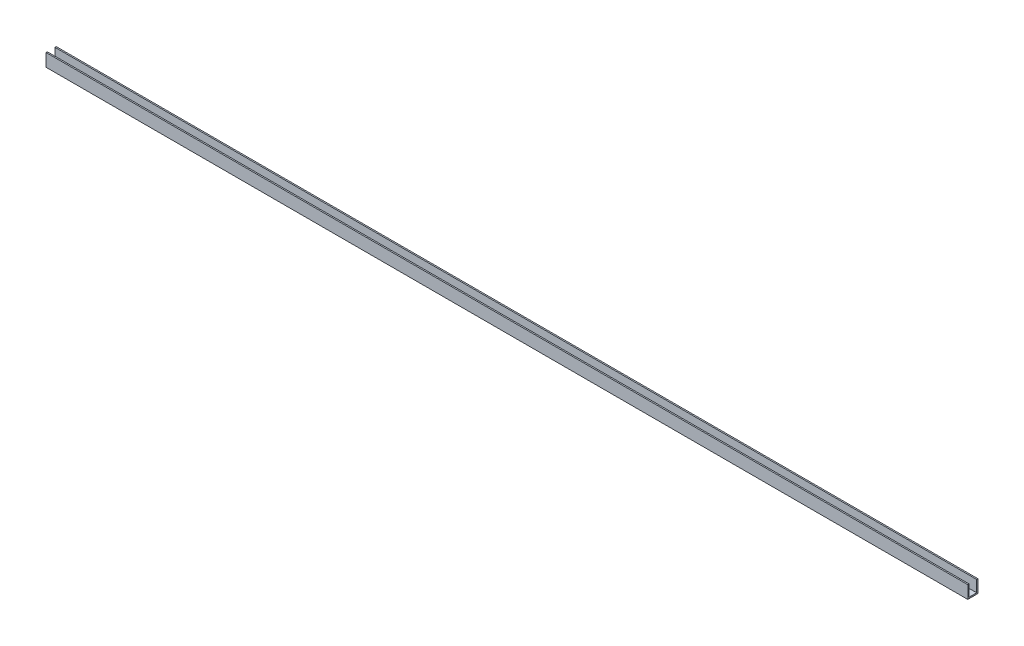
SolidWorks part; units mm, degrees
ref_plane "Front Plane" through (0, 0, 0) normal (0, 0, 1) x (1, 0, 0)
ref_plane "Top Plane" through (0, 0, 0) normal (0, 1, 0) x (1, 0, 0)
ref_plane "Right Plane" through (0, 0, 0) normal (1, 0, 0) x (0, 0, -1)
sketch "Sketch1" plane through (0, 0, 0) normal (1, 0, 0) x (0, 0, -1)
  line L0 (0, 21.5573) -> (0, -20.9315) construction
  line L1 (-36.1687, 0) -> (35.23, 0) construction
  line L2 (-4, 0) -> (4, 0)
  line L3 (4, 0) -> (4, 10)
  line L4 (4, 10) -> (3, 10)
  line L5 (3, 10) -> (3, 1)
  line L6 (3, 1) -> (-3, 1)
  line L7 (-3, 1) -> (-3, 10)
  line L8 (-3, 10) -> (-4, 10)
  line L9 (-4, 10) -> (-4, 0)
  dimension "D1" = 8
  dimension "D2" = 1
  dimension "D3" = 1
  dimension "D4" = 10
extrude "Boss-Extrude1" add sketch "Sketch1" along normal blind 720
ref_plane "Plane1" through (720, 10, 3) normal (-1, 0, 0) x (0, 0, 1)
